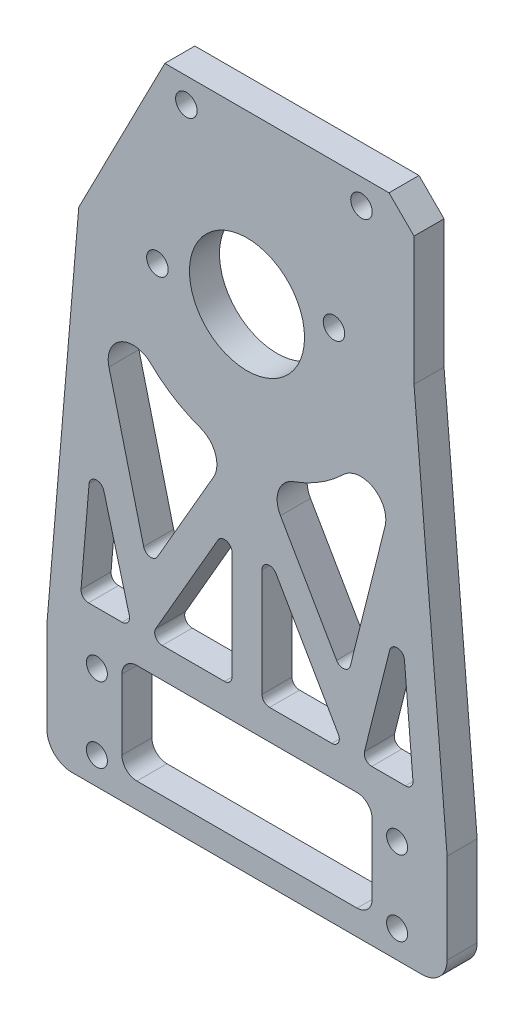
SolidWorks part; units mm, degrees
material "Thornel Mat VMA"
ref_plane "前视基准面" through (0, 0, 0) normal (0, 0, 1) x (1, 0, 0)
ref_plane "上视基准面" through (0, 0, 0) normal (0, 1, 0) x (1, 0, 0)
ref_plane "右视基准面" through (0, 0, 0) normal (1, 0, 0) x (0, 0, -1)
sketch "草图1" plane through (0, 0, 0) normal (0, 0, 1) x (1, 0, 0)
  line L0 (-40, 10) -> (-33.381, 88.3211)
  line L1 (-40, 10) -> (40, 10)
  line L2 (-40, 10) -> (-40, -10)
  line L3 (-40, -10) -> (40, -10)
  line L4 (40, 10) -> (40, -10)
  line L5 (-40, 10) -> (40, -10) construction
  line L6 (-40, -10) -> (40, 10) construction
  line L7 (-30, 7.5) -> (30, 7.5) construction
  line L8 (-30, 7.5) -> (-30, -7.5) construction
  line L9 (-30, -7.5) -> (30, -7.5) construction
  line L10 (30, 7.5) -> (30, -7.5) construction
  line L11 (-30, 7.5) -> (30, -7.5) construction
  line L12 (-30, -7.5) -> (30, 7.5) construction
  line L13 (33.381, 88.3211) -> (40, 10)
  circle A0 centre (0, 85.5) radius 33.5
  circle A1 centre (-30, -7.5) radius 2.1
  circle A2 centre (30, -7.5) radius 2.1
  circle A3 centre (30, 7.5) radius 2.1
  circle A4 centre (-30, 7.5) radius 2.1
  circle A5 centre (0, 85.5) radius 11.5
  point P0 (0, 0)
  point P6 (0, 0)
  dimension "D4" = 67
  dimension "D6" = 4.2
  dimension "D9" = 23
  dimension "D1" = 60
  dimension "D2" = 15
  dimension "D3" = 80
  dimension "D5" = 93
  dimension "D7" = 2
  dimension "D8" = 2
extrude "凸台-拉伸1" add sketch "草图1" along normal blind 6 contours A0 A5 | A0 L0 L1 L13 | L4 L1 L2 L3 A4 A3 A2 A1 region at (0, 35.2262, 0) region at (0, 0, 0) region at (0, 118.0525, 0)
sketch "草图3" plane through (0, 0, 6) normal (0, 0, 1) x (1, 0, 0)
  line L1 (-40, -10) -> (40, -10)
  line L2 (-40, -10) -> (-40, -13)
  line L3 (-40, -13) -> (40, -13)
  line L4 (40, -10) -> (40, -13)
  dimension "D1" = 3
extrude "凸台-拉伸2" add sketch "草图3" against normal up to surface (6 mm away) up to face at (11.5, 85.5, 0)
fillet "圆角1" radius 5 2 edges at (40, -13, 3) (-40, -13, 3)
sketch "草图4" plane through (0, 0, 6) normal (0, 0, 1) x (1, 0, 0)
  line L1 (33.381, 88.3211) -> (11.1486, 88.3211)
  line L2 (33.381, 88.3211) -> (33.381, 119)
  line L3 (33.381, 119) -> (-33.619, 119)
  line L4 (-33.619, 85.505) -> (-33.619, 119)
  line L5 (-11.5, 85.505) -> (-33.619, 85.505)
  line L6 (-40, 10) -> (-33.381, 88.3211) construction
  arc A0 (33.381, 88.3211) -> (-33.381, 88.3211) centre (0, 85.5) ccw construction
  arc A1 (11.1486, 88.3211) -> (-11.5, 85.505) centre (0, 85.5) ccw
  dimension "D1" = 23
  dimension "D2" = 67
extrude "凸台-拉伸3" add sketch "草图4" against normal up to surface (6 mm away) up to face at (11.5, 85.5, 0)
sketch "草图5" plane through (0, 0, 6) normal (0, 0, 1) x (1, 0, 0)
  circle A0 centre (-17.9014, 83.6185) radius 2
  circle A1 centre (17.3867, 90.1587) radius 2
  dimension "D1" = 4
extrude "切除-拉伸1" cut sketch "草图5" against normal through all
hole_wizard "M4 六角凹锥坑螺钉的锥形沉头孔1" positions "草图6" profile "草图7" countersink size "M4" standard "ISO"
sketch "草图6" plane through (0, 0, 0) normal (0, 0, -1) x (-1, 0, 0)
  point P0 (-17.3867, 90.1587)
  point P3 (17.9014, 83.6185)
sketch "草图7" plane through (17.3867, 90.1587, 0) normal (1, 0, 0) x (0, 1, 0)
  line L0 (0, 0) -> (0, 11.2919)
  line L1 (0, 11.2919) -> (2.15, 10)
  line L2 (2.15, 10) -> (2.15, 2.33)
  line L3 (2.15, 2.33) -> (4.48, 0)
  line L5 (4.48, 0) -> (0, 0)
  line L6 (-2.15, 2.33) -> (-4.48, 0) construction
  line L10 (0, 11.2919) -> (-2.15, 10) construction
  line L11 (0, -6.35) -> (0, 107.95) construction
  dimension "孔直径" = 4.3
  dimension "孔深度" = 10
  dimension "近端锥形沉头孔直径" = 8.96
  dimension "近端锥形沉头孔角度" = 90
  dimension "导头角度" = 118
sketch "草图8" plane through (0, 0, 6) normal (0, 0, 1) x (1, 0, 0)
  circle A0 centre (-12.119, 114) radius 2.1
  circle A1 centre (22.881, 114) radius 2.1
  dimension "D1" = 4.2
extrude "切除-拉伸2" cut sketch "草图8" against normal blind 10
hole_wizard "M4 六角凹锥坑螺钉的锥形沉头孔2" positions "草图9" profile "草图10" countersink size "M4" standard "ISO"
sketch "草图9" plane through (0, 0, 0) normal (0, 0, -1) x (-1, 0, 0)
  point P0 (-22.881, 114)
  point P3 (12.119, 114)
sketch "草图10" plane through (22.881, 114, 0) normal (1, 0, 0) x (0, 1, 0)
  line L0 (0, 0) -> (0, 11.2919)
  line L1 (0, 11.2919) -> (2.15, 10)
  line L2 (2.15, 10) -> (2.15, 2.33)
  line L3 (2.15, 2.33) -> (4.48, 0)
  line L5 (4.48, 0) -> (0, 0)
  line L6 (-2.15, 2.33) -> (-4.48, 0) construction
  line L10 (0, 11.2919) -> (-2.15, 10) construction
  line L11 (0, -6.35) -> (0, 107.95) construction
  dimension "孔直径" = 4.3
  dimension "孔深度" = 10
  dimension "近端锥形沉头孔直径" = 8.96
  dimension "近端锥形沉头孔角度" = 90
  dimension "导头角度" = 118
chamfer "倒角1" distance 5 angle 45 1 edges at (33.381, 119, 3)
sketch "草图11" plane through (0, 0, 6) normal (0, 0, 1) x (1, 0, 0)
  line L0 (-33.619, 119) -> (-16.4228, 119)
  line L1 (-33.619, 119) -> (-33.619, 85.505) construction
  line L2 (-16.4228, 119) -> (-33.619, 85.505)
  line L3 (-33.619, 85.505) -> (-33.619, 119)
  line L4 (28.381, 119) -> (-33.619, 119) construction
  dimension "D1" = 17.1962
  dimension "D2" = 33.495
extrude "切除-拉伸3" cut sketch "草图11" against normal through all
sketch "草图13" plane through (0, 0, 6) normal (0, 0, 1) x (1, 0, 0)
  line L0 (-24.8926, 50.1172) -> (-29.1546, 67.0817)
  line L1 (-25, 12) -> (25, 12)
  line L2 (-25, 12) -> (-25, -8)
  line L3 (-25, -8) -> (25, -8)
  line L4 (25, 12) -> (25, -8)
  line L5 (-25, 12) -> (25, -8) construction
  line L6 (-25, -8) -> (25, 12) construction
  line L7 (-17.1912, 19.4619) -> (-24.8926, 50.1172)
  line L11 (27.4023, 87.8158) -> (34.0213, 9.4947)
  line L12 (27.4023, 87.8158) -> (34.0213, 9.4947)
  line L13 (-33.3025, 18) -> (33.3025, 18)
  line L14 (-34.0213, 9.4947) -> (-27.6403, 84.9998)
  line L15 (-34.0213, 9.4947) -> (-27.6403, 84.9998)
  line L16 (0, 57.8552) -> (0, 18)
  line L17 (0, 57.8552) -> (-23.0104, 18)
  line L18 (0, 57.8552) -> (23.0104, 18)
  line L19 (23.0104, 18) -> (30.7118, 48.6553)
  line L20 (-23.0104, 18) -> (-30.8308, 47.2472)
  line L21 (-3, 57.8552) -> (-3, 18)
  line L22 (-2.5981, 59.3552) -> (-25.6085, 19.5)
  line L23 (-2.5981, 56.3552) -> (20.4123, 16.5)
  line L24 (3, 57.8552) -> (3, 18)
  line L25 (2.5981, 56.3552) -> (-20.4123, 16.5)
  line L26 (2.5981, 59.3552) -> (25.6085, 19.5)
  line L27 (17.1912, 19.4619) -> (24.8926, 50.1172)
  line L28 (24.8926, 50.1172) -> (29.1546, 67.0817)
  circle A0 centre (0, 85.5) radius 27.6448
  point P3 (0, 2)
  dimension "D1" = 2
  dimension "D2" = 20
  dimension "D3" = 50
  dimension "D6" = 6
  dimension "D7" = 60
  dimension "D8" = 60
  dimension "D4" = 6
  dimension "D5" = 6
  dimension "D9" = 3
  dimension "D10" = 3
  dimension "D11" = 6
extrude "切除-拉伸5" cut sketch "草图13" against normal blind 10 contours A0 L15 L0 L7 L22 | A0 L26 L27 L28 L12 | L23 L24 L13 | L21 L25 L13 | L13 L20 L15 | L19 L13 L12 | L2 L1 L4 L3 region at (-18.6067, 54.2272, 6) region at (-29.0479, 27.7491, 6) region at (-8.5154, 27.553, 6) region at (18.6067, 54.2272, 6) region at (8.5154, 27.553, 6) region at (29.0082, 28.2184, 6)
fillet "圆角3" radius 3 4 edges at (25, -8, 3) (-25, -8, 3) (-25, 12, 3) (25, 12, 3)
fillet "圆角4" radius 6 2 edges at (27.6403, 84.9998, 3) (-27.6403, 84.9998, 3)
fillet "圆角5" radius 5 2 edges at (3.3467, 58.0585, 3) (-3.3467, 58.0585, 3)
fillet "圆角6" radius 1.5 14 edges at (19.75, 29.6471, 3) (-3, 18, 3) (-19.5463, 18, 3) (-3, 46.659, 3) (-30.8308, 47.2472, 3) (-23.0104, 18, 3) (-19.75, 29.6471, 3) (30.7118, 48.6553, 3) (33.3025, 18, 3) (23.0104, 18, 3) (3, 46.659, 3) (19.5463, 18, 3) (3, 18, 3) (-33.3025, 18, 3)
fillet "圆角7" radius 5 2 edges at (29.1546, 67.0817, 3) (-29.1546, 67.0817, 3)
